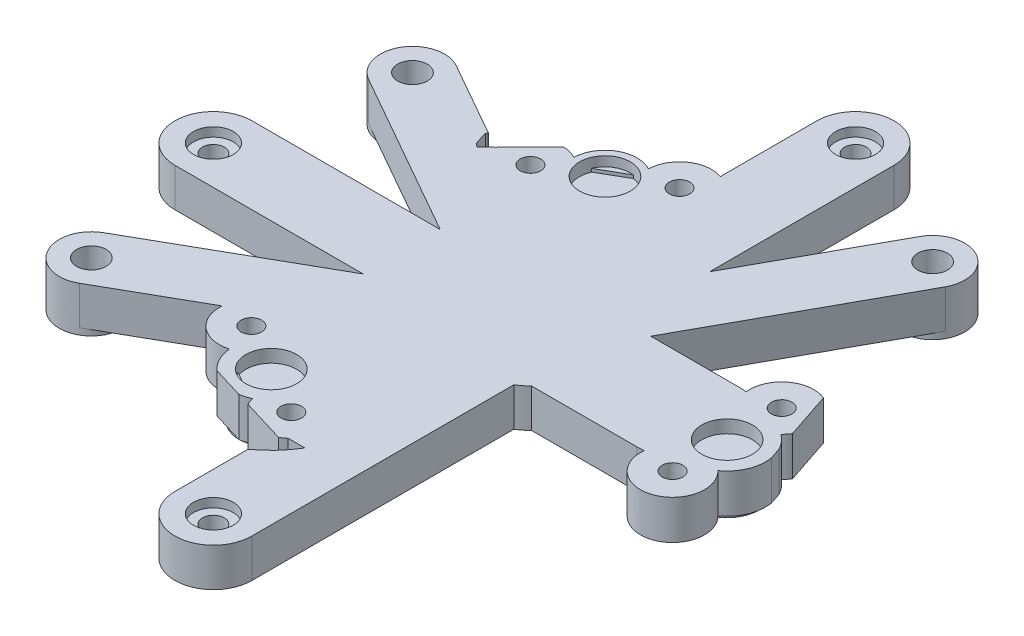
SolidWorks part; units mm, degrees
other "Fixed Star Plate Print Blank Left"
ref_plane "Front Plane" through (0, 0, 0) normal (0, 0, 1) x (1, 0, 0)
ref_plane "Top Plane" through (0, 0, 0) normal (0, 1, 0) x (1, 0, 0)
ref_plane "Right Plane" through (0, 0, 0) normal (1, 0, 0) x (0, 0, -1)
sketch3d "Base Outline Sketch datum points"
  point P0 (0, 71, 0)
  point P1 (10, 71, 0)
  point P2 (0, 71, -10)
ref_plane "Base Outline Sketch plane" through (0, 71, 0) normal (0, 1, 0) x (1, 0, 0)
sketch "Base Outline Sketch" plane through (0, 71, 0) normal (0, 1, 0) x (1, 0, 0)
  line L0 (-32.2917, 8) -> (-46.1853, 8)
  line L1 (-24.4227, 13.1376) -> (-22.0154, 5.909)
  line L2 (-20.9711, 2.7735) -> (-20.3706, 0.9703)
  line L3 (-48.7418, -8) -> (-32.2917, -8)
  line L4 (-50.2917, -50) -> (-50.2917, -9.2195)
  line L5 (-62.2917, -38.6002) -> (-62.2917, -50)
  line L6 (-58.0273, -34) -> (-60.6452, -34)
  line L7 (-61.5389, -34.6217) -> (-68.3642, -32.542)
  line L8 (-70.4166, -31.9166) -> (-75.3281, -30.42)
  line L9 (-97.8216, -29.3473) -> (-83.633, -21.2856)
  line L10 (-76.9729, -6) -> (-102.7617, -20.6527)
  line L11 (-106.2917, -6) -> (-76.9729, -6)
  line L12 (-76.9729, 6) -> (-106.2917, 6)
  line L13 (-102.7617, 20.6527) -> (-76.9729, 6)
  line L14 (-86.2562, 22.776) -> (-97.8216, 29.3473)
  line L15 (-86.2562, 22.776) -> (-86.3054, 22.6772)
  line L16 (-86.3054, 22.6772) -> (-86.3838, 22.4486)
  line L17 (-85.7572, 20.4132) -> (-85.2034, 19.9887)
  line L18 (-85.2034, 19.9887) -> (-83.8108, 21.3866)
  line L19 (-83.633, 21.2856) -> (-83.8108, 21.3866)
  line L20 (-83.6495, 21.5484) -> (-78.4893, 26.7281)
  line L21 (-62.2917, 50) -> (-62.2917, 34.9546)
  line L22 (-50.2917, 21.2843) -> (-50.2917, 50)
  line L23 (-38.6727, 42.4096) -> (-50.2917, 21.2843)
  line L24 (-46.1853, 8) -> (-29.9106, 37.5904)
  circle A0 centre (-71.2917, -25.9808) radius 3.95
  circle A1 centre (-63.9304, -30.2308) radius 1.6
  circle A2 centre (-26.2917, 0) radius 3.95
  circle A3 centre (-56.2917, -50) radius 3.1
  circle A4 centre (-26.2917, -8.5) radius 1.6
  circle A5 centre (-78.6529, -21.7308) radius 1.6
  circle A6 centre (-100.2917, -25) radius 2.3
  circle A7 centre (-71.2917, 25.9808) radius 3.95
  circle A8 centre (-34.2917, 40) radius 2.3
  circle A9 centre (-26.2917, 8.5) radius 1.6
  circle A10 centre (-63.9304, 30.2308) radius 1.6
  circle A11 centre (-56.2917, 50) radius 3.1
  circle A12 centre (-78.6529, 21.7308) radius 1.6
  circle A13 centre (-106.2917, 0) radius 3.1
  circle A14 centre (-100.2917, 25) radius 2.3
  arc A15 (-31.2594, 7.9331) -> (-32.2917, 8) centre (-32.2917, 0) ccw
  arc A16 (-24.4227, 13.1376) -> (-31.2594, 7.9331) centre (-26.2917, 8.5) ccw
  arc A17 (-22.8248, 4.8971) -> (-22.0154, 5.909) centre (-26.2917, 8.5) ccw
  arc A18 (-20.9711, 2.7735) -> (-22.8248, 4.8971) centre (-26.2917, 0) ccw
  arc A19 (-22.8248, -4.8971) -> (-20.3706, 0.9703) centre (-26.2917, 0) ccw
  arc A20 (-31.2594, -7.9331) -> (-22.8248, -4.8971) centre (-26.2917, -8.5) ccw
  arc A21 (-32.2917, -8) -> (-31.2594, -7.9331) centre (-32.2917, 0) ccw
  arc A22 (-50.2917, -9.2195) -> (-48.7418, -8) centre (-56.2917, 0) ccw
  arc A23 (-62.2917, -50) -> (-50.2917, -50) centre (-56.2917, -50) ccw
  arc A24 (-62.2917, -38.6002) -> (-58.0273, -34) centre (-71.2917, -25.9808) ccw
  arc A25 (-61.5389, -34.6217) -> (-60.6452, -34) centre (-63.9304, -30.2308) ccw
  arc A26 (-68.7841, -31.4316) -> (-68.3642, -32.542) centre (-63.9304, -30.2308) ccw
  arc A27 (-70.4166, -31.9166) -> (-68.7841, -31.4316) centre (-71.2917, -25.9808) ccw
  arc A28 (-77.266, -26.5346) -> (-75.3281, -30.42) centre (-71.2917, -25.9808) ccw
  arc A29 (-83.633, -21.2856) -> (-77.266, -26.5346) centre (-78.6529, -21.7308) ccw
  arc A30 (-100.2917, -30) -> (-97.8216, -29.3473) centre (-100.2917, -25) ccw
  arc A31 (-102.7617, -20.6527) -> (-100.2917, -30) centre (-100.2917, -25) ccw
  arc A32 (-106.2917, 6) -> (-106.2917, -6) centre (-106.2917, 0) ccw
  arc A33 (-97.8216, 29.3473) -> (-102.7617, 20.6527) centre (-100.2917, 25) ccw
  arc A34 (-86.3838, 22.4486) -> (-85.7572, 20.4132) centre (-71.2917, 25.9808) ccw
  arc A35 (-83.6495, 21.5484) -> (-83.633, 21.2856) centre (-78.6529, 21.7308) ccw
  arc A36 (-76.2892, 26.1368) -> (-78.4893, 26.7281) centre (-78.6529, 21.7308) ccw
  arc A37 (-68.928, 30.3868) -> (-76.2892, 26.1368) centre (-71.2917, 25.9808) ccw
  arc A38 (-68.7841, 31.4316) -> (-68.928, 30.3868) centre (-63.9304, 30.2308) ccw
  arc A39 (-62.2917, 34.9546) -> (-68.7841, 31.4316) centre (-63.9304, 30.2308) ccw
  arc A40 (-50.2917, 50) -> (-62.2917, 50) centre (-56.2917, 50) ccw
  arc A41 (-29.9106, 37.5904) -> (-38.6727, 42.4096) centre (-34.2917, 40) ccw
extrude "Base Outline" add sketch "Base Outline Sketch" against normal blind 1.4 separate body
sketch3d "Interface Profile 2 Sketch datum points"
  point P0 (0, 69.6, 0)
  point P1 (10, 69.6, 0)
  point P2 (0, 69.6, -10)
ref_plane "Interface Profile 2 Sketch plane" through (0, 69.6, 0) normal (0, 1, 0) x (1, 0, 0)
sketch "Interface Profile 2 Sketch" plane through (0, 69.6, 0) normal (0, 1, 0) x (1, 0, 0)
  line L0 (-32.2917, 8) -> (-46.1853, 8)
  line L1 (-24.4227, 13.1376) -> (-22.0154, 5.909)
  line L2 (-20.9711, 2.7735) -> (-20.3706, 0.9703)
  line L3 (-48.7418, -8) -> (-32.2917, -8)
  line L4 (-50.2917, -50) -> (-50.2917, -9.2195)
  line L5 (-62.2917, -38.6002) -> (-62.2917, -50)
  line L6 (-58.0273, -34) -> (-60.6452, -34)
  line L7 (-61.5389, -34.6217) -> (-68.3642, -32.542)
  line L8 (-70.4166, -31.9166) -> (-75.3281, -30.42)
  line L9 (-97.8216, -29.3473) -> (-83.633, -21.2856)
  line L10 (-76.9729, -6) -> (-102.7617, -20.6527)
  line L11 (-106.2917, -6) -> (-76.9729, -6)
  line L12 (-76.9729, 6) -> (-106.2917, 6)
  line L13 (-102.7617, 20.6527) -> (-76.9729, 6)
  line L14 (-86.2562, 22.776) -> (-97.8216, 29.3473)
  line L15 (-86.2562, 22.776) -> (-86.3054, 22.6772)
  line L16 (-86.3054, 22.6772) -> (-86.3838, 22.4486)
  line L17 (-85.7572, 20.4132) -> (-85.2034, 19.9887)
  line L18 (-85.2034, 19.9887) -> (-83.8108, 21.3866)
  line L19 (-83.633, 21.2856) -> (-83.8108, 21.3866)
  line L20 (-83.6495, 21.5484) -> (-78.4893, 26.7281)
  line L21 (-62.2917, 50) -> (-62.2917, 34.9546)
  line L22 (-50.2917, 21.2843) -> (-50.2917, 50)
  line L23 (-38.6727, 42.4096) -> (-50.2917, 21.2843)
  line L24 (-46.1853, 8) -> (-29.9106, 37.5904)
  circle A0 centre (-71.2917, -25.9808) radius 3.95
  circle A1 centre (-63.9304, -30.2308) radius 1.6
  circle A2 centre (-26.2917, 0) radius 3.95
  circle A3 centre (-56.2917, -50) radius 1.7
  circle A4 centre (-56.2917, 50) radius 1.7
  circle A5 centre (-106.2917, 0) radius 1.7
  circle A6 centre (-26.2917, -8.5) radius 1.6
  circle A7 centre (-78.6529, -21.7308) radius 1.6
  circle A8 centre (-100.2917, -25) radius 2.3
  circle A9 centre (-71.2917, 25.9808) radius 3.95
  circle A10 centre (-34.2917, 40) radius 2.3
  circle A11 centre (-26.2917, 8.5) radius 1.6
  circle A12 centre (-63.9304, 30.2308) radius 1.6
  circle A13 centre (-78.6529, 21.7308) radius 1.6
  circle A14 centre (-100.2917, 25) radius 2.3
  arc A15 (-31.2594, 7.9331) -> (-32.2917, 8) centre (-32.2917, 0) ccw
  arc A16 (-24.4227, 13.1376) -> (-31.2594, 7.9331) centre (-26.2917, 8.5) ccw
  arc A17 (-22.8248, 4.8971) -> (-22.0154, 5.909) centre (-26.2917, 8.5) ccw
  arc A18 (-20.9711, 2.7735) -> (-22.8248, 4.8971) centre (-26.2917, 0) ccw
  arc A19 (-22.8248, -4.8971) -> (-20.3706, 0.9703) centre (-26.2917, 0) ccw
  arc A20 (-31.2594, -7.9331) -> (-22.8248, -4.8971) centre (-26.2917, -8.5) ccw
  arc A21 (-32.2917, -8) -> (-31.2594, -7.9331) centre (-32.2917, 0) ccw
  arc A22 (-50.2917, -9.2195) -> (-48.7418, -8) centre (-56.2917, 0) ccw
  arc A23 (-62.2917, -50) -> (-50.2917, -50) centre (-56.2917, -50) ccw
  arc A24 (-62.2917, -38.6002) -> (-58.0273, -34) centre (-71.2917, -25.9808) ccw
  arc A25 (-61.5389, -34.6217) -> (-60.6452, -34) centre (-63.9304, -30.2308) ccw
  arc A26 (-68.7841, -31.4316) -> (-68.3642, -32.542) centre (-63.9304, -30.2308) ccw
  arc A27 (-70.4166, -31.9166) -> (-68.7841, -31.4316) centre (-71.2917, -25.9808) ccw
  arc A28 (-77.266, -26.5346) -> (-75.3281, -30.42) centre (-71.2917, -25.9808) ccw
  arc A29 (-83.633, -21.2856) -> (-77.266, -26.5346) centre (-78.6529, -21.7308) ccw
  arc A30 (-100.2917, -30) -> (-97.8216, -29.3473) centre (-100.2917, -25) ccw
  arc A31 (-102.7617, -20.6527) -> (-100.2917, -30) centre (-100.2917, -25) ccw
  arc A32 (-106.2917, 6) -> (-106.2917, -6) centre (-106.2917, 0) ccw
  arc A33 (-97.8216, 29.3473) -> (-102.7617, 20.6527) centre (-100.2917, 25) ccw
  arc A34 (-86.3838, 22.4486) -> (-85.7572, 20.4132) centre (-71.2917, 25.9808) ccw
  arc A35 (-83.6495, 21.5484) -> (-83.633, 21.2856) centre (-78.6529, 21.7308) ccw
  arc A36 (-76.2892, 26.1368) -> (-78.4893, 26.7281) centre (-78.6529, 21.7308) ccw
  arc A37 (-68.928, 30.3868) -> (-76.2892, 26.1368) centre (-71.2917, 25.9808) ccw
  arc A38 (-68.7841, 31.4316) -> (-68.928, 30.3868) centre (-63.9304, 30.2308) ccw
  arc A39 (-62.2917, 34.9546) -> (-68.7841, 31.4316) centre (-63.9304, 30.2308) ccw
  arc A40 (-50.2917, 50) -> (-62.2917, 50) centre (-56.2917, 50) ccw
  arc A41 (-29.9106, 37.5904) -> (-38.6727, 42.4096) centre (-34.2917, 40) ccw
extrude "Interface Profile 2" add sketch "Interface Profile 2 Sketch" against normal blind 0.1
sketch3d "Interface Profile 3 Sketch datum points"
  point P0 (0, 69.5, 0)
  point P1 (10, 69.5, 0)
  point P2 (0, 69.5, -10)
ref_plane "Interface Profile 3 Sketch plane" through (0, 69.5, 0) normal (0, 1, 0) x (1, 0, 0)
sketch "Interface Profile 3 Sketch" plane through (0, 69.5, 0) normal (0, 1, 0) x (1, 0, 0)
  line L0 (-70.8027, -29.9004) -> (-74.9306, -27.5171)
  line L1 (-23.1417, 2.3833) -> (-23.1417, -2.3833)
  line L2 (-74.9306, 27.5171) -> (-70.8027, 29.9004)
  line L3 (-32.2917, 8) -> (-46.1853, 8)
  line L4 (-24.4227, 13.1376) -> (-22.0154, 5.909)
  line L5 (-20.9711, 2.7735) -> (-20.3706, 0.9703)
  line L6 (-48.7418, -8) -> (-32.2917, -8)
  line L7 (-50.2917, -50) -> (-50.2917, -9.2195)
  line L8 (-62.2917, -38.6002) -> (-62.2917, -50)
  line L9 (-58.0273, -34) -> (-60.6452, -34)
  line L10 (-61.5389, -34.6217) -> (-68.3642, -32.542)
  line L11 (-70.4166, -31.9166) -> (-75.3281, -30.42)
  line L12 (-97.8216, -29.3473) -> (-83.633, -21.2856)
  line L13 (-76.9729, -6) -> (-102.7617, -20.6527)
  line L14 (-106.2917, -6) -> (-76.9729, -6)
  line L15 (-76.9729, 6) -> (-106.2917, 6)
  line L16 (-102.7617, 20.6527) -> (-76.9729, 6)
  line L17 (-86.2562, 22.776) -> (-97.8216, 29.3473)
  line L18 (-86.2562, 22.776) -> (-86.3054, 22.6772)
  line L19 (-86.3054, 22.6772) -> (-86.3838, 22.4486)
  line L20 (-85.7572, 20.4132) -> (-85.2034, 19.9887)
  line L21 (-85.2034, 19.9887) -> (-83.8108, 21.3866)
  line L22 (-83.633, 21.2856) -> (-83.8108, 21.3866)
  line L23 (-83.6495, 21.5484) -> (-78.4893, 26.7281)
  line L24 (-62.2917, 50) -> (-62.2917, 34.9546)
  line L25 (-50.2917, 21.2843) -> (-50.2917, 50)
  line L26 (-38.6727, 42.4096) -> (-50.2917, 21.2843)
  line L27 (-46.1853, 8) -> (-29.9106, 37.5904)
  arc A0 (-67.3417, -25.9808) -> (-70.8027, -29.9004) centre (-71.2917, -25.9808) cw
  arc A1 (-74.9306, -27.5171) -> (-67.3417, -25.9808) centre (-71.2917, -25.9808) cw
  circle A2 centre (-63.9304, -30.2308) radius 1.6
  arc A3 (-23.1417, -2.3833) -> (-23.1417, 2.3833) centre (-26.2917, 0) cw
  circle A4 centre (-56.2917, -50) radius 1.7
  circle A5 centre (-56.2917, 50) radius 1.7
  circle A6 centre (-106.2917, 0) radius 1.7
  circle A7 centre (-26.2917, -8.5) radius 1.6
  circle A8 centre (-78.6529, -21.7308) radius 1.6
  circle A9 centre (-100.2917, -25) radius 2.3
  arc A10 (-67.3417, 25.9808) -> (-74.9306, 27.5171) centre (-71.2917, 25.9808) cw
  arc A11 (-70.8027, 29.9004) -> (-67.3417, 25.9808) centre (-71.2917, 25.9808) cw
  circle A12 centre (-34.2917, 40) radius 2.3
  circle A13 centre (-26.2917, 8.5) radius 1.6
  circle A14 centre (-63.9304, 30.2308) radius 1.6
  circle A15 centre (-78.6529, 21.7308) radius 1.6
  circle A16 centre (-100.2917, 25) radius 2.3
  arc A17 (-31.2594, 7.9331) -> (-32.2917, 8) centre (-32.2917, 0) ccw
  arc A18 (-24.4227, 13.1376) -> (-31.2594, 7.9331) centre (-26.2917, 8.5) ccw
  arc A19 (-22.8248, 4.8971) -> (-22.0154, 5.909) centre (-26.2917, 8.5) ccw
  arc A20 (-20.9711, 2.7735) -> (-22.8248, 4.8971) centre (-26.2917, 0) ccw
  arc A21 (-22.8248, -4.8971) -> (-20.3706, 0.9703) centre (-26.2917, 0) ccw
  arc A22 (-31.2594, -7.9331) -> (-22.8248, -4.8971) centre (-26.2917, -8.5) ccw
  arc A23 (-32.2917, -8) -> (-31.2594, -7.9331) centre (-32.2917, 0) ccw
  arc A24 (-50.2917, -9.2195) -> (-48.7418, -8) centre (-56.2917, 0) ccw
  arc A25 (-62.2917, -50) -> (-50.2917, -50) centre (-56.2917, -50) ccw
  arc A26 (-62.2917, -38.6002) -> (-58.0273, -34) centre (-71.2917, -25.9808) ccw
  arc A27 (-61.5389, -34.6217) -> (-60.6452, -34) centre (-63.9304, -30.2308) ccw
  arc A28 (-68.7841, -31.4316) -> (-68.3642, -32.542) centre (-63.9304, -30.2308) ccw
  arc A29 (-70.4166, -31.9166) -> (-68.7841, -31.4316) centre (-71.2917, -25.9808) ccw
  arc A30 (-77.266, -26.5346) -> (-75.3281, -30.42) centre (-71.2917, -25.9808) ccw
  arc A31 (-83.633, -21.2856) -> (-77.266, -26.5346) centre (-78.6529, -21.7308) ccw
  arc A32 (-100.2917, -30) -> (-97.8216, -29.3473) centre (-100.2917, -25) ccw
  arc A33 (-102.7617, -20.6527) -> (-100.2917, -30) centre (-100.2917, -25) ccw
  arc A34 (-106.2917, 6) -> (-106.2917, -6) centre (-106.2917, 0) ccw
  arc A35 (-97.8216, 29.3473) -> (-102.7617, 20.6527) centre (-100.2917, 25) ccw
  arc A36 (-86.3838, 22.4486) -> (-85.7572, 20.4132) centre (-71.2917, 25.9808) ccw
  arc A37 (-83.6495, 21.5484) -> (-83.633, 21.2856) centre (-78.6529, 21.7308) ccw
  arc A38 (-76.2892, 26.1368) -> (-78.4893, 26.7281) centre (-78.6529, 21.7308) ccw
  arc A39 (-68.928, 30.3868) -> (-76.2892, 26.1368) centre (-71.2917, 25.9808) ccw
  arc A40 (-68.7841, 31.4316) -> (-68.928, 30.3868) centre (-63.9304, 30.2308) ccw
  arc A41 (-62.2917, 34.9546) -> (-68.7841, 31.4316) centre (-63.9304, 30.2308) ccw
  arc A42 (-50.2917, 50) -> (-62.2917, 50) centre (-56.2917, 50) ccw
  arc A43 (-29.9106, 37.5904) -> (-38.6727, 42.4096) centre (-34.2917, 40) ccw
extrude "Interface Profile 3" add sketch "Interface Profile 3 Sketch" against normal blind 0.5
sketch3d "Interface Profile 4 Sketch datum points"
  point P0 (0, 69, 0)
  point P1 (10, 69, 0)
  point P2 (0, 69, -10)
ref_plane "Interface Profile 4 Sketch plane" through (0, 69, 0) normal (0, 1, 0) x (1, 0, 0)
sketch "Interface Profile 4 Sketch" plane through (0, 69, 0) normal (0, 1, 0) x (1, 0, 0)
  line L0 (-32.2917, 8) -> (-46.1853, 8)
  line L1 (-24.4227, 13.1376) -> (-22.0154, 5.909)
  line L2 (-20.9711, 2.7735) -> (-20.3706, 0.9703)
  line L3 (-48.7418, -8) -> (-32.2917, -8)
  line L4 (-50.2917, -50) -> (-50.2917, -9.2195)
  line L5 (-62.2917, -38.6002) -> (-62.2917, -50)
  line L6 (-58.0273, -34) -> (-60.6452, -34)
  line L7 (-61.5389, -34.6217) -> (-68.3642, -32.542)
  line L8 (-70.4166, -31.9166) -> (-75.3281, -30.42)
  line L9 (-97.8216, -29.3473) -> (-83.633, -21.2856)
  line L10 (-76.9729, -6) -> (-102.7617, -20.6527)
  line L11 (-106.2917, -6) -> (-76.9729, -6)
  line L12 (-76.9729, 6) -> (-106.2917, 6)
  line L13 (-102.7617, 20.6527) -> (-76.9729, 6)
  line L14 (-86.2562, 22.776) -> (-97.8216, 29.3473)
  line L15 (-86.2562, 22.776) -> (-86.3054, 22.6772)
  line L16 (-86.3054, 22.6772) -> (-86.3838, 22.4486)
  line L17 (-85.7572, 20.4132) -> (-85.2034, 19.9887)
  line L18 (-85.2034, 19.9887) -> (-83.8108, 21.3866)
  line L19 (-83.633, 21.2856) -> (-83.8108, 21.3866)
  line L20 (-83.6495, 21.5484) -> (-78.4893, 26.7281)
  line L21 (-62.2917, 50) -> (-62.2917, 34.9546)
  line L22 (-50.2917, 21.2843) -> (-50.2917, 50)
  line L23 (-38.6727, 42.4096) -> (-50.2917, 21.2843)
  line L24 (-46.1853, 8) -> (-29.9106, 37.5904)
  circle A0 centre (-63.9304, -30.2308) radius 1.6
  circle A1 centre (-56.2917, -50) radius 1.7
  circle A2 centre (-56.2917, 50) radius 1.7
  circle A3 centre (-106.2917, 0) radius 1.7
  circle A4 centre (-26.2917, -8.5) radius 1.6
  circle A5 centre (-78.6529, -21.7308) radius 1.6
  circle A6 centre (-100.2917, -25) radius 2.3
  circle A7 centre (-34.2917, 40) radius 2.3
  circle A8 centre (-26.2917, 8.5) radius 1.6
  circle A9 centre (-63.9304, 30.2308) radius 1.6
  circle A10 centre (-78.6529, 21.7308) radius 1.6
  circle A11 centre (-100.2917, 25) radius 2.3
  arc A12 (-31.2594, 7.9331) -> (-32.2917, 8) centre (-32.2917, 0) ccw
  arc A13 (-24.4227, 13.1376) -> (-31.2594, 7.9331) centre (-26.2917, 8.5) ccw
  arc A14 (-22.8248, 4.8971) -> (-22.0154, 5.909) centre (-26.2917, 8.5) ccw
  arc A15 (-20.9711, 2.7735) -> (-22.8248, 4.8971) centre (-26.2917, 0) ccw
  arc A16 (-22.8248, -4.8971) -> (-20.3706, 0.9703) centre (-26.2917, 0) ccw
  arc A17 (-31.2594, -7.9331) -> (-22.8248, -4.8971) centre (-26.2917, -8.5) ccw
  arc A18 (-32.2917, -8) -> (-31.2594, -7.9331) centre (-32.2917, 0) ccw
  arc A19 (-50.2917, -9.2195) -> (-48.7418, -8) centre (-56.2917, 0) ccw
  arc A20 (-62.2917, -50) -> (-50.2917, -50) centre (-56.2917, -50) ccw
  arc A21 (-62.2917, -38.6002) -> (-58.0273, -34) centre (-71.2917, -25.9808) ccw
  arc A22 (-61.5389, -34.6217) -> (-60.6452, -34) centre (-63.9304, -30.2308) ccw
  arc A23 (-68.7841, -31.4316) -> (-68.3642, -32.542) centre (-63.9304, -30.2308) ccw
  arc A24 (-70.4166, -31.9166) -> (-68.7841, -31.4316) centre (-71.2917, -25.9808) ccw
  arc A25 (-77.266, -26.5346) -> (-75.3281, -30.42) centre (-71.2917, -25.9808) ccw
  arc A26 (-83.633, -21.2856) -> (-77.266, -26.5346) centre (-78.6529, -21.7308) ccw
  arc A27 (-100.2917, -30) -> (-97.8216, -29.3473) centre (-100.2917, -25) ccw
  arc A28 (-102.7617, -20.6527) -> (-100.2917, -30) centre (-100.2917, -25) ccw
  arc A29 (-106.2917, 6) -> (-106.2917, -6) centre (-106.2917, 0) ccw
  arc A30 (-97.8216, 29.3473) -> (-102.7617, 20.6527) centre (-100.2917, 25) ccw
  arc A31 (-86.3838, 22.4486) -> (-85.7572, 20.4132) centre (-71.2917, 25.9808) ccw
  arc A32 (-83.6495, 21.5484) -> (-83.633, 21.2856) centre (-78.6529, 21.7308) ccw
  arc A33 (-76.2892, 26.1368) -> (-78.4893, 26.7281) centre (-78.6529, 21.7308) ccw
  arc A34 (-68.928, 30.3868) -> (-76.2892, 26.1368) centre (-71.2917, 25.9808) ccw
  arc A35 (-68.7841, 31.4316) -> (-68.928, 30.3868) centre (-63.9304, 30.2308) ccw
  arc A36 (-62.2917, 34.9546) -> (-68.7841, 31.4316) centre (-63.9304, 30.2308) ccw
  arc A37 (-50.2917, 50) -> (-62.2917, 50) centre (-56.2917, 50) ccw
  arc A38 (-29.9106, 37.5904) -> (-38.6727, 42.4096) centre (-34.2917, 40) ccw
extrude "Interface Profile 4" add sketch "Interface Profile 4 Sketch" against normal blind 1.5
sketch3d "Interface Profile 5 Sketch datum points"
  point P0 (0, 67.5, 0)
  point P1 (10, 67.5, 0)
  point P2 (0, 67.5, -10)
ref_plane "Interface Profile 5 Sketch plane" through (0, 67.5, 0) normal (0, 1, 0) x (1, 0, 0)
sketch "Interface Profile 5 Sketch" plane through (0, 67.5, 0) normal (0, 1, 0) x (1, 0, 0)
  line L0 (-59.5825, -50) -> (-57.9371, -47.15)
  line L1 (-57.9371, -52.85) -> (-59.5825, -50)
  line L2 (-57.9371, -47.15) -> (-54.6462, -47.15)
  line L3 (-54.6462, 52.85) -> (-53.0008, 50)
  line L4 (-57.9371, 52.85) -> (-54.6462, 52.85)
  line L5 (-53.0008, 50) -> (-54.6462, 47.15)
  line L6 (-59.5825, 50) -> (-57.9371, 52.85)
  line L7 (-57.9371, 47.15) -> (-59.5825, 50)
  line L8 (-54.6462, 47.15) -> (-57.9371, 47.15)
  line L9 (-104.6462, 2.85) -> (-103.0008, 0)
  line L10 (-107.9371, 2.85) -> (-104.6462, 2.85)
  line L11 (-103.0008, 0) -> (-104.6462, -2.85)
  line L12 (-109.5825, 0) -> (-107.9371, 2.85)
  line L13 (-107.9371, -2.85) -> (-109.5825, 0)
  line L14 (-104.6462, -2.85) -> (-107.9371, -2.85)
  line L15 (-54.6462, -52.85) -> (-57.9371, -52.85)
  line L16 (-54.6462, -47.15) -> (-53.0008, -50)
  line L17 (-53.0008, -50) -> (-54.6462, -52.85)
  line L18 (-32.2917, 8) -> (-46.1853, 8)
  line L19 (-24.4227, 13.1376) -> (-22.0154, 5.909)
  line L20 (-20.9711, 2.7735) -> (-20.3706, 0.9703)
  line L21 (-48.7418, -8) -> (-32.2917, -8)
  line L22 (-50.2917, -50) -> (-50.2917, -9.2195)
  line L23 (-62.2917, -38.6002) -> (-62.2917, -50)
  line L24 (-58.0273, -34) -> (-60.6452, -34)
  line L25 (-61.5389, -34.6217) -> (-68.3642, -32.542)
  line L26 (-70.4166, -31.9166) -> (-75.3281, -30.42)
  line L27 (-97.8216, -29.3473) -> (-83.633, -21.2856)
  line L28 (-76.9729, -6) -> (-102.7617, -20.6527)
  line L29 (-106.2917, -6) -> (-76.9729, -6)
  line L30 (-76.9729, 6) -> (-106.2917, 6)
  line L31 (-102.7617, 20.6527) -> (-76.9729, 6)
  line L32 (-86.2562, 22.776) -> (-97.8216, 29.3473)
  line L33 (-86.2562, 22.776) -> (-86.3054, 22.6772)
  line L34 (-86.3054, 22.6772) -> (-86.3838, 22.4486)
  line L35 (-85.7572, 20.4132) -> (-85.2034, 19.9887)
  line L36 (-85.2034, 19.9887) -> (-83.8108, 21.3866)
  line L37 (-83.633, 21.2856) -> (-83.8108, 21.3866)
  line L38 (-83.6495, 21.5484) -> (-78.4893, 26.7281)
  line L39 (-62.2917, 50) -> (-62.2917, 34.9546)
  line L40 (-50.2917, 21.2843) -> (-50.2917, 50)
  line L41 (-38.6727, 42.4096) -> (-50.2917, 21.2843)
  line L42 (-46.1853, 8) -> (-29.9106, 37.5904)
  circle A0 centre (-63.9304, -30.2308) radius 1.6
  circle A1 centre (-26.2917, -8.5) radius 1.6
  circle A2 centre (-78.6529, -21.7308) radius 1.6
  circle A3 centre (-100.2917, -25) radius 2.3
  circle A4 centre (-34.2917, 40) radius 2.3
  circle A5 centre (-26.2917, 8.5) radius 1.6
  circle A6 centre (-63.9304, 30.2308) radius 1.6
  circle A7 centre (-78.6529, 21.7308) radius 1.6
  circle A8 centre (-100.2917, 25) radius 2.3
  arc A9 (-31.2594, 7.9331) -> (-32.2917, 8) centre (-32.2917, 0) ccw
  arc A10 (-24.4227, 13.1376) -> (-31.2594, 7.9331) centre (-26.2917, 8.5) ccw
  arc A11 (-22.8248, 4.8971) -> (-22.0154, 5.909) centre (-26.2917, 8.5) ccw
  arc A12 (-20.9711, 2.7735) -> (-22.8248, 4.8971) centre (-26.2917, 0) ccw
  arc A13 (-22.8248, -4.8971) -> (-20.3706, 0.9703) centre (-26.2917, 0) ccw
  arc A14 (-31.2594, -7.9331) -> (-22.8248, -4.8971) centre (-26.2917, -8.5) ccw
  arc A15 (-32.2917, -8) -> (-31.2594, -7.9331) centre (-32.2917, 0) ccw
  arc A16 (-50.2917, -9.2195) -> (-48.7418, -8) centre (-56.2917, 0) ccw
  arc A17 (-62.2917, -50) -> (-50.2917, -50) centre (-56.2917, -50) ccw
  arc A18 (-62.2917, -38.6002) -> (-58.0273, -34) centre (-71.2917, -25.9808) ccw
  arc A19 (-61.5389, -34.6217) -> (-60.6452, -34) centre (-63.9304, -30.2308) ccw
  arc A20 (-68.7841, -31.4316) -> (-68.3642, -32.542) centre (-63.9304, -30.2308) ccw
  arc A21 (-70.4166, -31.9166) -> (-68.7841, -31.4316) centre (-71.2917, -25.9808) ccw
  arc A22 (-77.266, -26.5346) -> (-75.3281, -30.42) centre (-71.2917, -25.9808) ccw
  arc A23 (-83.633, -21.2856) -> (-77.266, -26.5346) centre (-78.6529, -21.7308) ccw
  arc A24 (-100.2917, -30) -> (-97.8216, -29.3473) centre (-100.2917, -25) ccw
  arc A25 (-102.7617, -20.6527) -> (-100.2917, -30) centre (-100.2917, -25) ccw
  arc A26 (-106.2917, 6) -> (-106.2917, -6) centre (-106.2917, 0) ccw
  arc A27 (-97.8216, 29.3473) -> (-102.7617, 20.6527) centre (-100.2917, 25) ccw
  arc A28 (-86.3838, 22.4486) -> (-85.7572, 20.4132) centre (-71.2917, 25.9808) ccw
  arc A29 (-83.6495, 21.5484) -> (-83.633, 21.2856) centre (-78.6529, 21.7308) ccw
  arc A30 (-76.2892, 26.1368) -> (-78.4893, 26.7281) centre (-78.6529, 21.7308) ccw
  arc A31 (-68.928, 30.3868) -> (-76.2892, 26.1368) centre (-71.2917, 25.9808) ccw
  arc A32 (-68.7841, 31.4316) -> (-68.928, 30.3868) centre (-63.9304, 30.2308) ccw
  arc A33 (-62.2917, 34.9546) -> (-68.7841, 31.4316) centre (-63.9304, 30.2308) ccw
  arc A34 (-50.2917, 50) -> (-62.2917, 50) centre (-56.2917, 50) ccw
  arc A35 (-29.9106, 37.5904) -> (-38.6727, 42.4096) centre (-34.2917, 40) ccw
extrude "Interface Profile 5" add sketch "Interface Profile 5 Sketch" against normal blind 0.5
sketch3d "Interface Profile 6 Sketch datum points"
  point P0 (0, 67, 0)
  point P1 (10, 67, 0)
  point P2 (0, 67, -10)
ref_plane "Interface Profile 6 Sketch plane" through (0, 67, 0) normal (0, 1, 0) x (1, 0, 0)
sketch "Interface Profile 6 Sketch" plane through (0, 67, 0) normal (0, 1, 0) x (1, 0, 0)
  line L0 (-59.5825, -50) -> (-57.9371, -47.15)
  line L1 (-57.9371, -52.85) -> (-59.5825, -50)
  line L2 (-57.9371, -47.15) -> (-54.6462, -47.15)
  line L3 (-54.6462, 52.85) -> (-53.0008, 50)
  line L4 (-57.9371, 52.85) -> (-54.6462, 52.85)
  line L5 (-53.0008, 50) -> (-54.6462, 47.15)
  line L6 (-59.5825, 50) -> (-57.9371, 52.85)
  line L7 (-57.9371, 47.15) -> (-59.5825, 50)
  line L8 (-54.6462, 47.15) -> (-57.9371, 47.15)
  line L9 (-104.6462, 2.85) -> (-103.0008, 0)
  line L10 (-107.9371, 2.85) -> (-104.6462, 2.85)
  line L11 (-103.0008, 0) -> (-104.6462, -2.85)
  line L12 (-109.5825, 0) -> (-107.9371, 2.85)
  line L13 (-107.9371, -2.85) -> (-109.5825, 0)
  line L14 (-104.6462, -2.85) -> (-107.9371, -2.85)
  line L15 (-54.6462, -52.85) -> (-57.9371, -52.85)
  line L16 (-54.6462, -47.15) -> (-53.0008, -50)
  line L17 (-53.0008, -50) -> (-54.6462, -52.85)
  line L18 (-32.2917, 8) -> (-46.1853, 8)
  line L19 (-24.4227, 13.1376) -> (-22.0154, 5.909)
  line L20 (-20.9711, 2.7735) -> (-20.3706, 0.9703)
  line L21 (-48.7418, -8) -> (-32.2917, -8)
  line L22 (-50.2917, -50) -> (-50.2917, -9.2195)
  line L23 (-62.2917, -38.6002) -> (-62.2917, -50)
  line L24 (-58.0273, -34) -> (-60.6452, -34)
  line L25 (-61.5389, -34.6217) -> (-68.3642, -32.542)
  line L26 (-70.4166, -31.9166) -> (-75.3281, -30.42)
  line L27 (-97.8216, -29.3473) -> (-83.633, -21.2856)
  line L28 (-76.9729, -6) -> (-102.7617, -20.6527)
  line L29 (-106.2917, -6) -> (-76.9729, -6)
  line L30 (-76.9729, 6) -> (-106.2917, 6)
  line L31 (-102.7617, 20.6527) -> (-76.9729, 6)
  line L32 (-86.2562, 22.776) -> (-97.8216, 29.3473)
  line L33 (-86.2562, 22.776) -> (-86.3054, 22.6772)
  line L34 (-86.3054, 22.6772) -> (-86.3838, 22.4486)
  line L35 (-85.7572, 20.4132) -> (-85.2034, 19.9887)
  line L36 (-85.2034, 19.9887) -> (-83.8108, 21.3866)
  line L37 (-83.633, 21.2856) -> (-83.8108, 21.3866)
  line L38 (-83.6495, 21.5484) -> (-78.4893, 26.7281)
  line L39 (-62.2917, 50) -> (-62.2917, 34.9546)
  line L40 (-50.2917, 21.2843) -> (-50.2917, 50)
  line L41 (-38.6727, 42.4096) -> (-50.2917, 21.2843)
  line L42 (-46.1853, 8) -> (-29.9106, 37.5904)
  circle A0 centre (-63.9304, -30.2308) radius 1.1
  circle A1 centre (-26.2917, -8.5) radius 1.1
  circle A2 centre (-78.6529, -21.7308) radius 1.1
  circle A3 centre (-100.2917, -25) radius 2.3
  circle A4 centre (-34.2917, 40) radius 2.3
  circle A5 centre (-26.2917, 8.5) radius 1.1
  circle A6 centre (-63.9304, 30.2308) radius 1.1
  circle A7 centre (-78.6529, 21.7308) radius 1.1
  circle A8 centre (-100.2917, 25) radius 2.3
  arc A9 (-31.2594, 7.9331) -> (-32.2917, 8) centre (-32.2917, 0) ccw
  arc A10 (-24.4227, 13.1376) -> (-31.2594, 7.9331) centre (-26.2917, 8.5) ccw
  arc A11 (-22.8248, 4.8971) -> (-22.0154, 5.909) centre (-26.2917, 8.5) ccw
  arc A12 (-20.9711, 2.7735) -> (-22.8248, 4.8971) centre (-26.2917, 0) ccw
  arc A13 (-22.8248, -4.8971) -> (-20.3706, 0.9703) centre (-26.2917, 0) ccw
  arc A14 (-31.2594, -7.9331) -> (-22.8248, -4.8971) centre (-26.2917, -8.5) ccw
  arc A15 (-32.2917, -8) -> (-31.2594, -7.9331) centre (-32.2917, 0) ccw
  arc A16 (-50.2917, -9.2195) -> (-48.7418, -8) centre (-56.2917, 0) ccw
  arc A17 (-62.2917, -50) -> (-50.2917, -50) centre (-56.2917, -50) ccw
  arc A18 (-62.2917, -38.6002) -> (-58.0273, -34) centre (-71.2917, -25.9808) ccw
  arc A19 (-61.5389, -34.6217) -> (-60.6452, -34) centre (-63.9304, -30.2308) ccw
  arc A20 (-68.7841, -31.4316) -> (-68.3642, -32.542) centre (-63.9304, -30.2308) ccw
  arc A21 (-70.4166, -31.9166) -> (-68.7841, -31.4316) centre (-71.2917, -25.9808) ccw
  arc A22 (-77.266, -26.5346) -> (-75.3281, -30.42) centre (-71.2917, -25.9808) ccw
  arc A23 (-83.633, -21.2856) -> (-77.266, -26.5346) centre (-78.6529, -21.7308) ccw
  arc A24 (-100.2917, -30) -> (-97.8216, -29.3473) centre (-100.2917, -25) ccw
  arc A25 (-102.7617, -20.6527) -> (-100.2917, -30) centre (-100.2917, -25) ccw
  arc A26 (-106.2917, 6) -> (-106.2917, -6) centre (-106.2917, 0) ccw
  arc A27 (-97.8216, 29.3473) -> (-102.7617, 20.6527) centre (-100.2917, 25) ccw
  arc A28 (-86.3838, 22.4486) -> (-85.7572, 20.4132) centre (-71.2917, 25.9808) ccw
  arc A29 (-83.6495, 21.5484) -> (-83.633, 21.2856) centre (-78.6529, 21.7308) ccw
  arc A30 (-76.2892, 26.1368) -> (-78.4893, 26.7281) centre (-78.6529, 21.7308) ccw
  arc A31 (-68.928, 30.3868) -> (-76.2892, 26.1368) centre (-71.2917, 25.9808) ccw
  arc A32 (-68.7841, 31.4316) -> (-68.928, 30.3868) centre (-63.9304, 30.2308) ccw
  arc A33 (-62.2917, 34.9546) -> (-68.7841, 31.4316) centre (-63.9304, 30.2308) ccw
  arc A34 (-50.2917, 50) -> (-62.2917, 50) centre (-56.2917, 50) ccw
  arc A35 (-29.9106, 37.5904) -> (-38.6727, 42.4096) centre (-34.2917, 40) ccw
extrude "Interface Profile 6" add sketch "Interface Profile 6 Sketch" against normal blind 1.3
sketch3d "Interface Profile 7 Sketch datum points"
  point P0 (0, 65.7, 0)
  point P1 (10, 65.7, 0)
  point P2 (0, 65.7, -10)
ref_plane "Interface Profile 7 Sketch plane" through (0, 65.7, 0) normal (0, 1, 0) x (1, 0, 0)
sketch "Interface Profile 7 Sketch" plane through (0, 65.7, 0) normal (0, 1, 0) x (1, 0, 0)
  line L0 (-59.5825, -50) -> (-57.9371, -47.15)
  line L1 (-57.9371, -52.85) -> (-59.5825, -50)
  line L2 (-57.9371, -47.15) -> (-54.6462, -47.15)
  line L3 (-54.6462, 52.85) -> (-53.0008, 50)
  line L4 (-57.9371, 52.85) -> (-54.6462, 52.85)
  line L5 (-53.0008, 50) -> (-54.6462, 47.15)
  line L6 (-59.5825, 50) -> (-57.9371, 52.85)
  line L7 (-57.9371, 47.15) -> (-59.5825, 50)
  line L8 (-54.6462, 47.15) -> (-57.9371, 47.15)
  line L9 (-104.6462, 2.85) -> (-103.0008, 0)
  line L10 (-107.9371, 2.85) -> (-104.6462, 2.85)
  line L11 (-103.0008, 0) -> (-104.6462, -2.85)
  line L12 (-109.5825, 0) -> (-107.9371, 2.85)
  line L13 (-107.9371, -2.85) -> (-109.5825, 0)
  line L14 (-104.6462, -2.85) -> (-107.9371, -2.85)
  line L15 (-54.6462, -52.85) -> (-57.9371, -52.85)
  line L16 (-54.6462, -47.15) -> (-53.0008, -50)
  line L17 (-53.0008, -50) -> (-54.6462, -52.85)
  line L18 (-32.2917, 8) -> (-46.1853, 8)
  line L19 (-24.4227, 13.1376) -> (-22.0154, 5.909)
  line L20 (-20.9711, 2.7735) -> (-20.3706, 0.9703)
  line L21 (-48.7418, -8) -> (-32.2917, -8)
  line L22 (-50.2917, -50) -> (-50.2917, -9.2195)
  line L23 (-62.2917, -38.6002) -> (-62.2917, -50)
  line L24 (-58.0273, -34) -> (-60.6452, -34)
  line L25 (-61.5389, -34.6217) -> (-68.3642, -32.542)
  line L26 (-70.4166, -31.9166) -> (-75.3281, -30.42)
  line L27 (-97.8216, -29.3473) -> (-83.633, -21.2856)
  line L28 (-76.9729, -6) -> (-102.7617, -20.6527)
  line L29 (-106.2917, -6) -> (-76.9729, -6)
  line L30 (-76.9729, 6) -> (-106.2917, 6)
  line L31 (-102.7617, 20.6527) -> (-76.9729, 6)
  line L32 (-86.2562, 22.776) -> (-97.8216, 29.3473)
  line L33 (-86.2562, 22.776) -> (-86.3054, 22.6772)
  line L34 (-86.3054, 22.6772) -> (-86.3838, 22.4486)
  line L35 (-85.7572, 20.4132) -> (-85.2034, 19.9887)
  line L36 (-85.2034, 19.9887) -> (-83.8108, 21.3866)
  line L37 (-83.633, 21.2856) -> (-83.8108, 21.3866)
  line L38 (-83.6495, 21.5484) -> (-78.4893, 26.7281)
  line L39 (-62.2917, 50) -> (-62.2917, 34.9546)
  line L40 (-50.2917, 21.2843) -> (-50.2917, 50)
  line L41 (-38.6727, 42.4096) -> (-50.2917, 21.2843)
  line L42 (-46.1853, 8) -> (-29.9106, 37.5904)
  circle A0 centre (-100.2917, -25) radius 2.3
  circle A1 centre (-34.2917, 40) radius 2.3
  circle A2 centre (-100.2917, 25) radius 2.3
  arc A3 (-31.2594, 7.9331) -> (-32.2917, 8) centre (-32.2917, 0) ccw
  arc A4 (-24.4227, 13.1376) -> (-31.2594, 7.9331) centre (-26.2917, 8.5) ccw
  arc A5 (-22.8248, 4.8971) -> (-22.0154, 5.909) centre (-26.2917, 8.5) ccw
  arc A6 (-20.9711, 2.7735) -> (-22.8248, 4.8971) centre (-26.2917, 0) ccw
  arc A7 (-22.8248, -4.8971) -> (-20.3706, 0.9703) centre (-26.2917, 0) ccw
  arc A8 (-31.2594, -7.9331) -> (-22.8248, -4.8971) centre (-26.2917, -8.5) ccw
  arc A9 (-32.2917, -8) -> (-31.2594, -7.9331) centre (-32.2917, 0) ccw
  arc A10 (-50.2917, -9.2195) -> (-48.7418, -8) centre (-56.2917, 0) ccw
  arc A11 (-62.2917, -50) -> (-50.2917, -50) centre (-56.2917, -50) ccw
  arc A12 (-62.2917, -38.6002) -> (-58.0273, -34) centre (-71.2917, -25.9808) ccw
  arc A13 (-61.5389, -34.6217) -> (-60.6452, -34) centre (-63.9304, -30.2308) ccw
  arc A14 (-68.7841, -31.4316) -> (-68.3642, -32.542) centre (-63.9304, -30.2308) ccw
  arc A15 (-70.4166, -31.9166) -> (-68.7841, -31.4316) centre (-71.2917, -25.9808) ccw
  arc A16 (-77.266, -26.5346) -> (-75.3281, -30.42) centre (-71.2917, -25.9808) ccw
  arc A17 (-83.633, -21.2856) -> (-77.266, -26.5346) centre (-78.6529, -21.7308) ccw
  arc A18 (-100.2917, -30) -> (-97.8216, -29.3473) centre (-100.2917, -25) ccw
  arc A19 (-102.7617, -20.6527) -> (-100.2917, -30) centre (-100.2917, -25) ccw
  arc A20 (-106.2917, 6) -> (-106.2917, -6) centre (-106.2917, 0) ccw
  arc A21 (-97.8216, 29.3473) -> (-102.7617, 20.6527) centre (-100.2917, 25) ccw
  arc A22 (-86.3838, 22.4486) -> (-85.7572, 20.4132) centre (-71.2917, 25.9808) ccw
  arc A23 (-83.6495, 21.5484) -> (-83.633, 21.2856) centre (-78.6529, 21.7308) ccw
  arc A24 (-76.2892, 26.1368) -> (-78.4893, 26.7281) centre (-78.6529, 21.7308) ccw
  arc A25 (-68.928, 30.3868) -> (-76.2892, 26.1368) centre (-71.2917, 25.9808) ccw
  arc A26 (-68.7841, 31.4316) -> (-68.928, 30.3868) centre (-63.9304, 30.2308) ccw
  arc A27 (-62.2917, 34.9546) -> (-68.7841, 31.4316) centre (-63.9304, 30.2308) ccw
  arc A28 (-50.2917, 50) -> (-62.2917, 50) centre (-56.2917, 50) ccw
  arc A29 (-29.9106, 37.5904) -> (-38.6727, 42.4096) centre (-34.2917, 40) ccw
extrude "Interface Profile 7" add sketch "Interface Profile 7 Sketch" against normal blind 0.7
sketch3d "Interface Profile 8 Sketch datum points"
  point P0 (0, 65, 0)
  point P1 (10, 65, 0)
  point P2 (0, 65, -10)
ref_plane "Interface Profile 8 Sketch plane" through (0, 65, 0) normal (0, 1, 0) x (1, 0, 0)
sketch "Interface Profile 8 Sketch" plane through (0, 65, 0) normal (0, 1, 0) x (1, 0, 0)
  line L0 (-24.4227, 13.1376) -> (-22.0154, 5.909)
  line L1 (-20.9711, 2.7735) -> (-20.3706, 0.9703)
  line L2 (-61.5389, -34.6217) -> (-68.3642, -32.542)
  line L3 (-70.4166, -31.9166) -> (-75.3281, -30.42)
  line L4 (-83.6495, 21.5484) -> (-78.4893, 26.7281)
  arc A0 (-65.3173, -25.4269) -> (-73.7992, -20.5299) centre (-71.2917, -25.9808) ccw
  arc A1 (-61.5389, -34.6217) -> (-65.3173, -25.4269) centre (-63.9304, -30.2308) ccw
  arc A2 (-73.7992, -20.5299) -> (-77.266, -26.5346) centre (-78.6529, -21.7308) ccw
  arc A3 (-66.2941, 25.8247) -> (-65.3173, 25.4269) centre (-63.9304, 30.2308) ccw
  arc A4 (-73.6553, 21.5747) -> (-66.2941, 25.8247) centre (-71.2917, 25.9808) ccw
  arc A5 (-65.3173, 25.4269) -> (-68.7841, 31.4316) centre (-63.9304, 30.2308) ccw
  arc A6 (-29.7585, 4.8971) -> (-29.7585, -4.8971) centre (-26.2917, 0) ccw
  arc A7 (-24.4227, 13.1376) -> (-29.7585, 4.8971) centre (-26.2917, 8.5) ccw
  arc A8 (-29.7585, -4.8971) -> (-22.8248, -4.8971) centre (-26.2917, -8.5) ccw
  circle A9 centre (-100.2917, -25) radius 2.3
  circle A10 centre (-34.2917, 40) radius 2.3
  circle A11 centre (-100.2917, 25) radius 2.3
  arc A12 (-22.8248, 4.8971) -> (-22.0154, 5.909) centre (-26.2917, 8.5) ccw
  arc A13 (-20.9711, 2.7735) -> (-22.8248, 4.8971) centre (-26.2917, 0) ccw
  arc A14 (-22.8248, -4.8971) -> (-20.3706, 0.9703) centre (-26.2917, 0) ccw
  arc A15 (-68.7841, -31.4316) -> (-68.3642, -32.542) centre (-63.9304, -30.2308) ccw
  arc A16 (-70.4166, -31.9166) -> (-68.7841, -31.4316) centre (-71.2917, -25.9808) ccw
  arc A17 (-77.266, -26.5346) -> (-75.3281, -30.42) centre (-71.2917, -25.9808) ccw
  arc A18 (-100.2917, -30) -> (-97.8216, -29.3473) centre (-100.2917, -25) ccw
  arc A19 (-97.8216, -29.3473) -> (-100.2917, -30) centre (-100.2917, -25) ccw
  circle A20 centre (-100.2917, 25) radius 5
  arc A21 (-83.6495, 21.5484) -> (-73.6553, 21.5747) centre (-78.6529, 21.7308) ccw
  arc A22 (-76.2892, 26.1368) -> (-78.4893, 26.7281) centre (-78.6529, 21.7308) ccw
  arc A23 (-68.928, 30.3868) -> (-76.2892, 26.1368) centre (-71.2917, 25.9808) ccw
  arc A24 (-68.7841, 31.4316) -> (-68.928, 30.3868) centre (-63.9304, 30.2308) ccw
  circle A25 centre (-34.2917, 40) radius 5
extrude "Interface Profile 8" add sketch "Interface Profile 8 Sketch" against normal blind 0.1
sketch3d "Interface Profile 9 Sketch datum points"
  point P0 (0, 64.9, 0)
  point P1 (10, 64.9, 0)
  point P2 (0, 64.9, -10)
ref_plane "Interface Profile 9 Sketch plane" through (0, 64.9, 0) normal (0, 1, 0) x (1, 0, 0)
sketch "Interface Profile 9 Sketch" plane through (0, 64.9, 0) normal (0, 1, 0) x (1, 0, 0)
  circle A0 centre (-71.2917, -25.9808) radius 5
  circle A1 centre (-26.2917, 0) radius 5
  circle A2 centre (-100.2917, -25) radius 2.3
  circle A3 centre (-34.2917, 40) radius 2.3
  circle A4 centre (-100.2917, 25) radius 2.3
  arc A5 (-100.2917, -30) -> (-97.8216, -29.3473) centre (-100.2917, -25) ccw
  arc A6 (-97.8216, -29.3473) -> (-100.2917, -30) centre (-100.2917, -25) ccw
  circle A7 centre (-100.2917, 25) radius 5
  circle A8 centre (-71.2917, 25.9808) radius 5
  circle A9 centre (-34.2917, 40) radius 5
extrude "Interface Profile 9" add sketch "Interface Profile 9 Sketch" against normal blind 0.9
